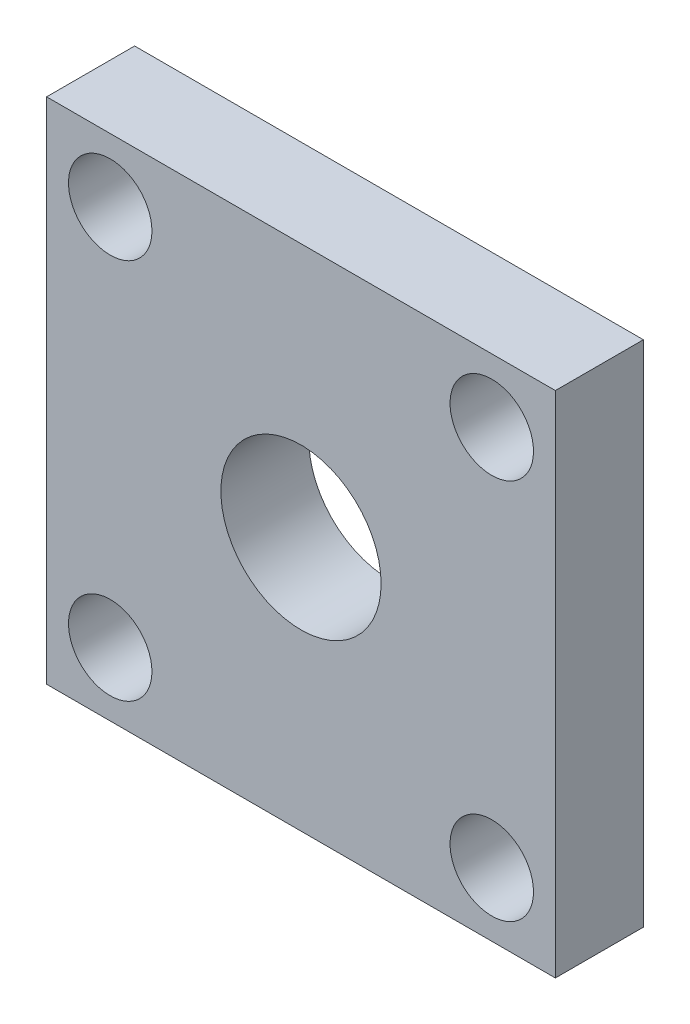
SolidWorks part; units mm, degrees
ref_plane "Front Plane" through (0, 0, 0) normal (0, 0, 1) x (1, 0, 0)
ref_plane "Top Plane" through (0, 0, 0) normal (0, 1, 0) x (1, 0, 0)
ref_plane "Right Plane" through (0, 0, 0) normal (1, 0, 0) x (0, 0, -1)
sketch "Sketch1" plane through (0, 0, 0) normal (0, 0, 1) x (1, 0, 0)
  line L0 (12.7, 25.4) -> (12.7, 0) construction
  line L1 (0, 0) -> (25.4, 0)
  line L2 (0, 0) -> (0, 25.4)
  line L3 (0, 25.4) -> (25.4, 25.4)
  line L4 (25.4, 0) -> (25.4, 25.4)
  line L5 (0, 12.7) -> (25.4, 12.7) construction
  circle A0 centre (3.175, 3.175) radius 2.0828
  circle A1 centre (3.175, 22.225) radius 2.0828
  circle A2 centre (22.225, 22.225) radius 2.0828
  circle A3 centre (22.225, 3.175) radius 2.0828
  circle A4 centre (12.7, 12.7) radius 4
  dimension "D1" = 4.1656
  dimension "D8" = 8
  dimension "D2" = 19.05
  dimension "D3" = 19.05
  dimension "D4" = 25.4
  dimension "D5" = 25.4
  dimension "D6" = 19.05
  dimension "D7" = 19.05
extrude "Boss-Extrude1" add sketch "Sketch1" along normal blind 4.3942
